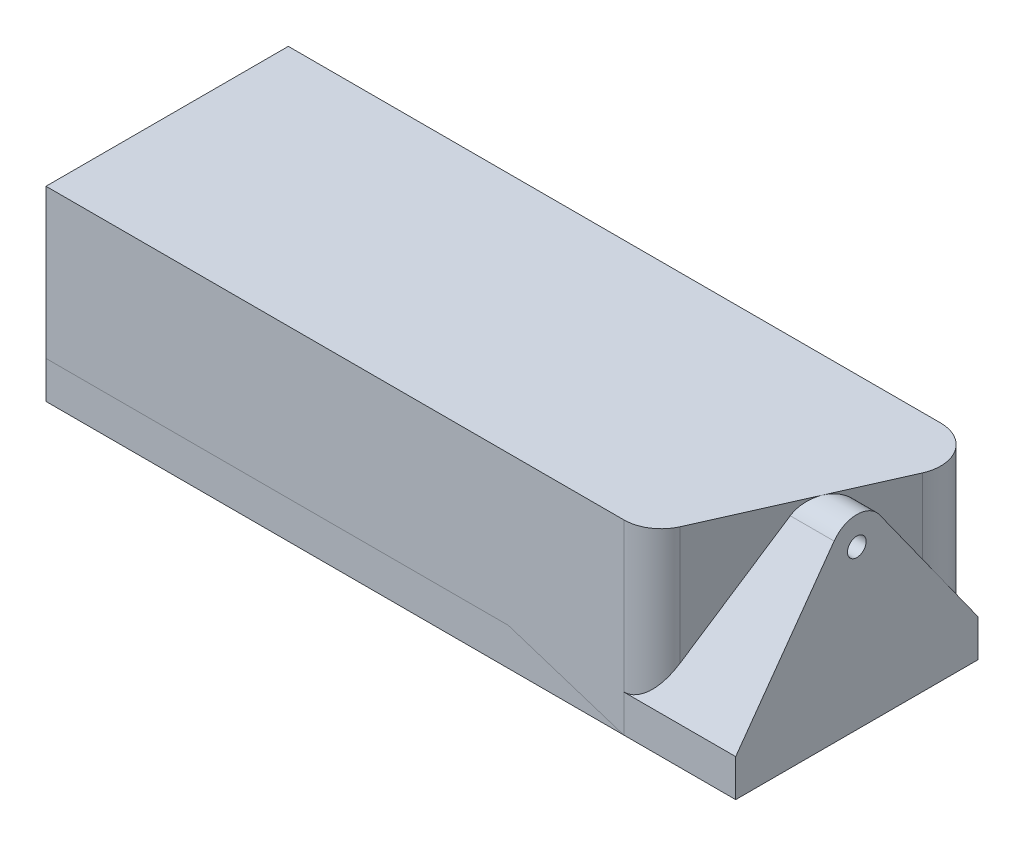
SolidWorks part; units mm, degrees
ref_plane "Front Plane" through (0, 0, 0) normal (0, 0, 1) x (1, 0, 0)
ref_plane "Top Plane" through (0, 0, 0) normal (0, 1, 0) x (1, 0, 0)
ref_plane "Right Plane" through (0, 0, 0) normal (1, 0, 0) x (0, 0, -1)
sketch "Sketch1" plane through (0, 0, 0) normal (0, 1, 0) x (1, 0, 0)
  line L0 (0, -10.3187) -> (0, 10.3187)
  line L1 (0, 10.3187) -> (55.5625, 10.3188)
  line L2 (58.4639, 5.8543) -> (52.1139, -8.4332)
  line L3 (49.2125, -10.3187) -> (0, -10.3187)
  arc A0 (55.5625, 10.3188) -> (58.4639, 5.8543) centre (55.5625, 7.1437) cw
  arc A1 (52.1139, -8.4332) -> (49.2125, -10.3187) centre (49.2125, -7.1437) cw
  point P4 (0, 0)
  point P11 (46.0375, 10.3187)
  dimension "D4" = 3.175
  dimension "D1" = 20.6375
  dimension "D2" = 46.0375
  dimension "D3" = 9.525
  dimension "D5" = 6.35
sketch "Sketch2" plane through (0, 0, 0) normal (0, 0, 1) x (1, 0, 0)
  line L0 (0, 0) -> (0, 3.175)
  line L1 (0, 3.175) -> (1.5875, 3.175)
  line L2 (1.5875, 3.175) -> (1.5875, 15.875)
  line L3 (1.5875, 15.875) -> (3.9688, 15.875)
  line L4 (3.9688, 15.875) -> (3.9688, 3.175)
  line L5 (3.9688, 3.175) -> (7.1438, 3.175)
  line L6 (7.1438, 3.175) -> (7.1438, 15.875)
  line L7 (7.1438, 15.875) -> (9.525, 15.875)
  line L8 (9.525, 15.875) -> (9.525, 3.175)
  line L9 (9.525, 3.175) -> (58.7375, 3.175)
  line L10 (58.7375, 3.175) -> (58.7375, 0)
  line L11 (58.7375, 0) -> (0, 0)
  dimension "D1" = 3.175
  dimension "D2" = 1.5875
  dimension "D3" = 12.7
  dimension "D4" = 2.3813
  dimension "D5" = 3.175
  dimension "D6" = 58.7375
sketch "Sketch3" plane through (0, 0, 0) normal (1, 0, 0) x (0, 0, -1)
  line L0 (10.3187, 0) -> (-10.3187, 0)
  line L2 (-10.3187, 0) -> (-10.3187, 3.175)
  line L3 (-10.3187, 3.175) -> (-1.936, 14.8802)
  line L4 (1.936, 14.8802) -> (10.3187, 3.175)
  line L5 (10.3187, 3.175) -> (10.3187, 0)
  arc A0 (-1.936, 14.8802) -> (1.936, 14.8802) centre (0, 13.4937) cw
  circle A1 centre (0, 13.4937) radius 0.7937
  point P4 (0, 0)
  dimension "D4" = 2.3813
  dimension "D1" = 20.6375
  dimension "D5" = 1.5875
  dimension "D2" = 3.175
  dimension "D3" = 10.3187
extrude "Boss-Extrude1" add sketch "Sketch1" along normal blind 15.875
extrude "Boss-Extrude2" add sketch "Sketch2" along normal blind 10.3187 and the other way blind 10.3187 separate body
extrude "Boss-Extrude3" add sketch "Sketch3" along normal blind 58.7375 separate body
equation "\"D6@Sketch2\"= \"D2@Sketch1\" + \"D3@Sketch1\" + \"D4@Sketch1\""
equation "\"D1@Sketch3\" = \"D1@Sketch1\""
equation "\"D2@Sketch3\"= \"D1@Sketch2\""
equation "\"D3@Sketch2\"= \"D3@Sketch3\" + \"D4@Sketch3\""
